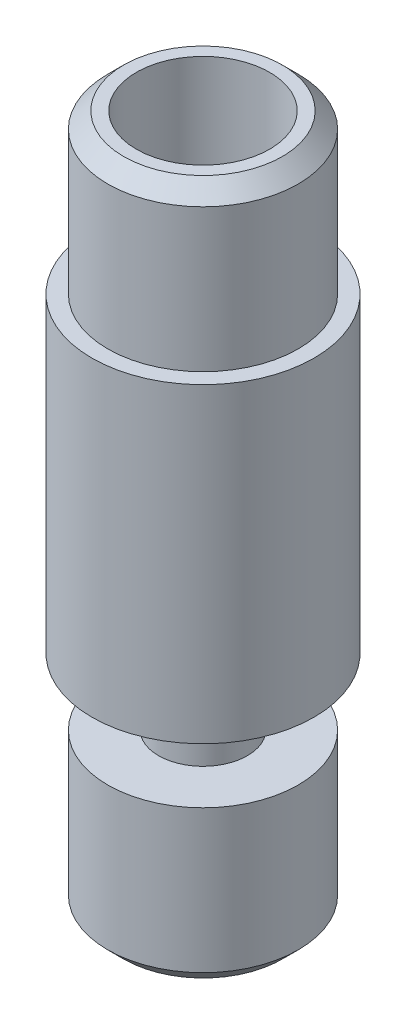
SolidWorks part; units mm, degrees
material "1060 Alloy"
ref_plane "Front Plane" through (0, 0, 0) normal (0, 0, 1) x (1, 0, 0)
ref_plane "Top Plane" through (0, 0, 0) normal (0, 1, 0) x (1, 0, 0)
ref_plane "Right Plane" through (0, 0, 0) normal (1, 0, 0) x (0, 0, -1)
ref_plane "Plane1" through (0, 0, 0) normal (0, 0, -1) x (-1, 0, 0)
sketch "Sketch1" plane through (0, 0, 0) normal (0, 0, -1) x (-1, 0, 0)
  line L0 (-2.5, 0) -> (-1, 0)
  line L1 (-1, 0) -> (-1, 15.8)
  line L2 (-1, 15.8) -> (-2.1, 16.9)
  line L3 (-2.1, 16.9) -> (-2.1, 21.9)
  line L4 (-2.1, 21.9) -> (-2.5, 21.9)
  line L5 (-2.5, 21.9) -> (-3, 21.4)
  line L6 (-3, 21.4) -> (-3, 16.9)
  line L7 (-3, 16.9) -> (-3.5, 16.9)
  line L8 (-3.5, 16.9) -> (-3.5, 7.1)
  line L9 (-3.5, 7.1) -> (-1.4, 7.1)
  line L10 (-1.4, 7.1) -> (-1.4, 5)
  line L11 (-1.4, 5) -> (-3, 5)
  line L12 (-3, 5) -> (-3, 0.5)
  line L13 (-3, 0.5) -> (-2.5, 0)
  line L14 (0, 0) -> (0, 21.9) construction
revolve "Revolve1" add sketch "Sketch1" angle 360 about L14 reverse direction yes
